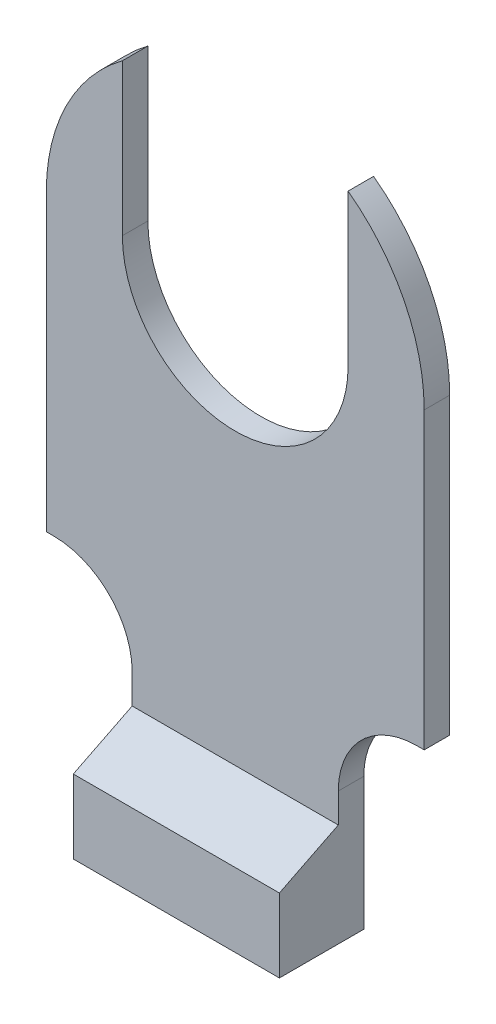
SolidWorks part; units mm, degrees
ref_plane "Спереди" through (0, 0, 0) normal (0, 0, 1) x (1, 0, 0)
ref_plane "Сверху" through (0, 0, 0) normal (0, 1, 0) x (1, 0, 0)
ref_plane "Справа" through (0, 0, 0) normal (1, 0, 0) x (0, 0, -1)
sketch "Эскиз1" plane through (0, 0, 0) normal (0, 0, 1) x (1, 0, 0)
  line L0 (-4.6, 0) -> (-4.6, 6.1749)
  line L1 (7.7, -20.6) -> (-7.7, -20.6)
  line L2 (7.7, -20.6) -> (7.7, 0)
  line L3 (4.6, 0) -> (4.6, 6.1749)
  line L4 (-7.7, -20.6) -> (-7.7, 0)
  arc A0 (7.7, 0) -> (4.6, 6.1749) centre (0, 0) ccw
  arc A1 (-4.6, 0) -> (4.6, 0) centre (0, 0) ccw
  arc A2 (-4.6, 6.1749) -> (-7.7, 0) centre (0, 0) ccw
  point P0 (0, 0)
  point P3 (0, -20.6)
  dimension "D3" = 9.2
  dimension "D1" = 20.6
  dimension "D2" = 15.4
extrude "Бобышка-Вытянуть1" add sketch "Эскиз1" along normal blind 1.04
sketch "Эскиз3" plane through (0, 0, 1.04) normal (0, 0, 1) x (1, 0, 0)
  line L0 (0, 0) -> (0, -20.6) construction
  line L1 (-7.7, -20.6) -> (-4.2, -20.6)
  line L2 (-7.7, -20.6) -> (-7.7, -12)
  line L3 (-7.7, -12) -> (-7.4, -12)
  line L4 (-4.2, -20.6) -> (-4.2, -15.2)
  line L5 (-7.7, -20.6) -> (7.7, -20.6) construction
  line L6 (4.2, -20.6) -> (4.2, -15.2)
  line L7 (7.7, -12) -> (7.4, -12)
  line L8 (7.7, -20.6) -> (7.7, -12)
  line L9 (7.7, -20.6) -> (4.2, -20.6)
  arc A0 (-4.2, -15.2) -> (-7.4, -12) centre (-7.4, -15.2) ccw
  arc A1 (4.2, -15.2) -> (7.4, -12) centre (7.4, -15.2) cw
  dimension "D3" = 3.2
  dimension "D1" = 4.2
  dimension "D2" = 8.6
extrude "Вырез-Вытянуть1" cut sketch "Эскиз3" against normal up to surface (1.04 mm away) up to face at (0, -4.0895, 0)
sketch "Эскиз4" plane through (0, 0, 1.04) normal (0, 0, 1) x (1, 0, 0)
  line L0 (4.2, -15.2) -> (4.2, -20.6) construction
  line L1 (-4.2, -20.6) -> (4.2, -20.6)
  line L2 (-4.2, -20.6) -> (-4.2, -17.6)
  line L3 (-4.2, -17.6) -> (4.2, -17.6)
  line L4 (4.2, -20.6) -> (4.2, -17.6)
  dimension "D1" = 3
extrude "Бобышка-Вытянуть2" add sketch "Эскиз4" along normal blind 2.4
chamfer "Фаска1" distance 1.2 distance2 2.4 1 edges at (0, -17.6, 1.04) first distance on face at (0, -7.4136, 1.04)
